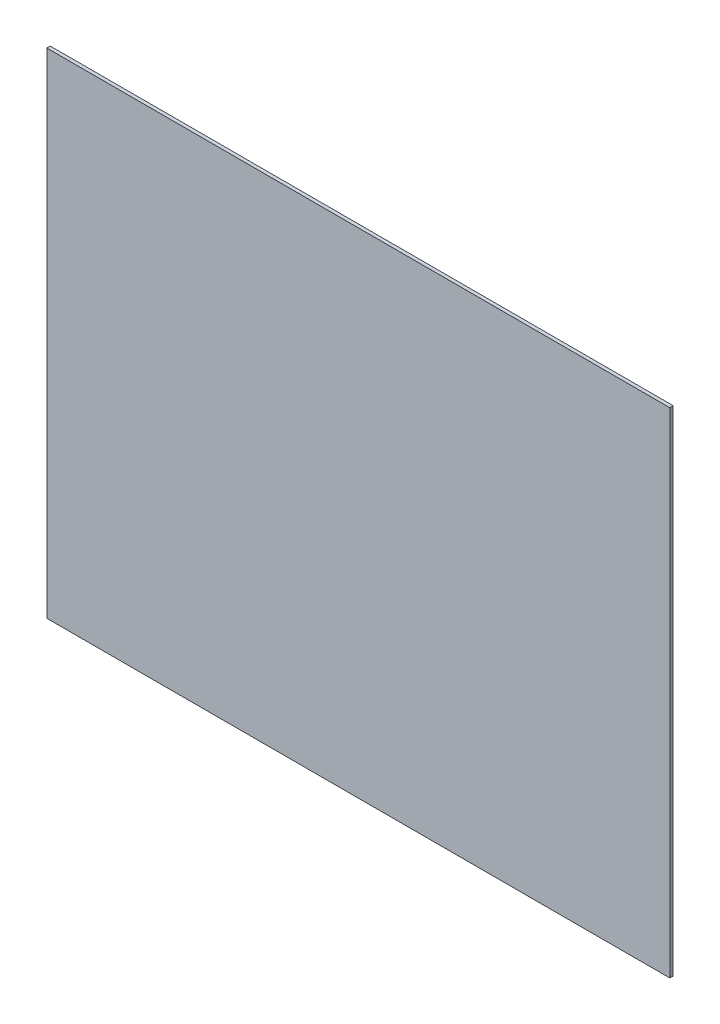
SolidWorks part; units mm, degrees
material "Acrylic (Medium-high impact)"
ref_plane "Front Plane" through (0, 0, 0) normal (0, 0, 1) x (1, 0, 0)
ref_plane "Top Plane" through (0, 0, 0) normal (0, 1, 0) x (1, 0, 0)
ref_plane "Right Plane" through (0, 0, 0) normal (1, 0, 0) x (0, 0, -1)
sketch "Sketch1" plane through (0, 0, 0) normal (0, 0, 1) x (1, 0, 0)
  line L1 (-289.5, -229.5) -> (289.5, -229.5)
  line L2 (-289.5, -229.5) -> (-289.5, 229.5)
  line L3 (-289.5, 229.5) -> (289.5, 229.5)
  line L4 (289.5, -229.5) -> (289.5, 229.5)
  line L5 (-289.5, -229.5) -> (289.5, 229.5) construction
  line L6 (-289.5, 229.5) -> (289.5, -229.5) construction
  point P0 (0, 0)
  dimension "D1" = 579
  dimension "D2" = 459
extrude "Boss-Extrude1" add sketch "Sketch1" along normal mid plane 3.175
